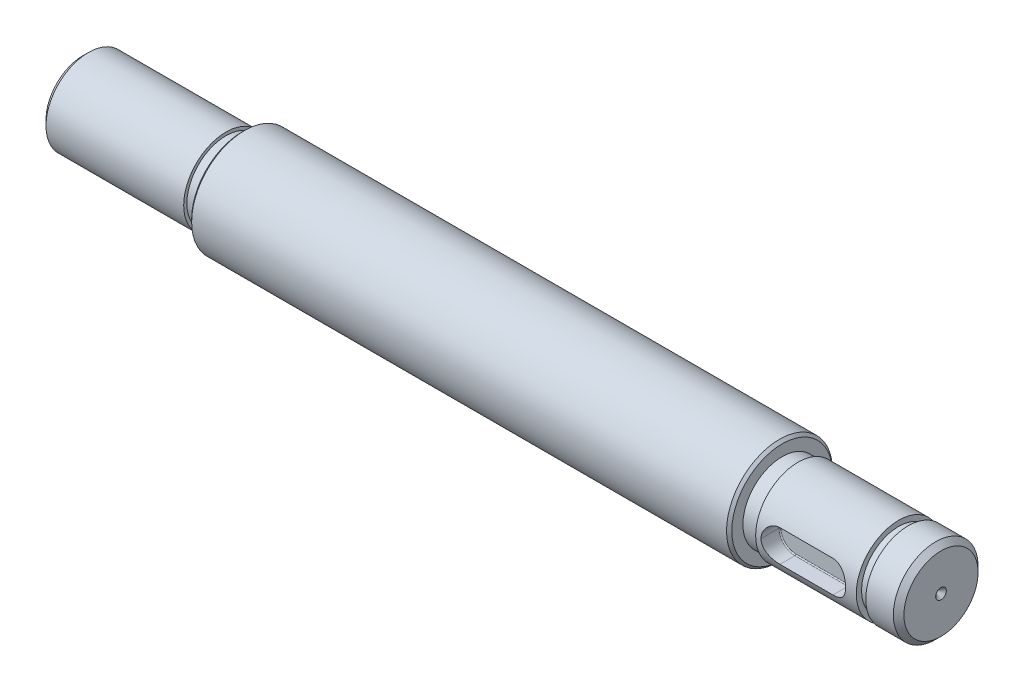
SolidWorks part; units mm, degrees
ref_plane "Front Plane" through (0, 0, 0) normal (0, 0, 1) x (1, 0, 0)
ref_plane "Top Plane" through (0, 0, 0) normal (0, 1, 0) x (1, 0, 0)
ref_plane "Right Plane" through (0, 0, 0) normal (1, 0, 0) x (0, 0, -1)
sketch "Sketch1" plane through (0, 0, 0) normal (0, 0, 1) x (1, 0, 0)
  line L0 (0, 0) -> (81, 0) construction
  line L1 (0, 4) -> (15, 4)
  line L2 (15, 4) -> (15, 4.75)
  line L3 (15.25, 5) -> (65.75, 5)
  line L4 (66, 4.75) -> (66, 4)
  line L5 (66, 4) -> (81, 4)
  line L6 (0, 4) -> (0, 0)
  line L7 (81, 0) -> (81, 4)
  line L8 (65.75, 5) -> (66, 4.75)
  line L9 (15, 4.75) -> (15.25, 5)
  line L10 (81, 0) -> (0, 0)
  dimension "D1" = 45
  dimension "D" = 10
  dimension "L_s_1" = 51
  dimension "LA" = 15
  dimension "LB" = 15
  dimension "L" = 81
  dimension "D2" = 45
revolve "Revolve1" add sketch "Sketch1" angle 360 about L0
cosmetic thread "Cosmetic Thread1" [suppressed] parameters "MA"=5, "TD_s"=6.619
cosmetic thread "Cosmetic Thread2" [suppressed] parameters "MSA"=5, "TD_s"=6.619
cosmetic thread "Cosmetic Thread3" [suppressed] parameters "MMA"=5, "TD_s"=6.619
cosmetic thread "Cosmetic Thread4" [suppressed] parameters "MC"=5, "TD_s"=8.344
cosmetic thread "Cosmetic Thread5" [suppressed] parameters "MSC"=5, "TD_s"=8.344
cosmetic thread "Cosmetic Thread6" [suppressed] parameters "MMC"=5, "TD_s"=8.344
cosmetic thread "Cosmetic Thread7" [suppressed] parameters "MD"=5, "TD_s"=8.344
cosmetic thread "Cosmetic Thread8" [suppressed] parameters "MSD"=5, "TD_s"=8.344
cosmetic thread "Cosmetic Thread9" [suppressed] parameters "MMD"=5, "TD_s"=8.344
cosmetic thread "Cosmetic Thread10" [suppressed] parameters "MB"=5, "TD_s"=6.619
cosmetic thread "Cosmetic Thread11" [suppressed] parameters "MSB"=5, "TD_s"=6.619
cosmetic thread "Cosmetic Thread12" [suppressed] parameters "MMB"=5, "TD_s"=6.619
chamfer "Chamfer1" distance 0.5 angle 45 2 edges at (81, 0, 4) (0, 0, 4)
sketch "Sketch2" plane through (0, 0, 0) normal (0, 0, 1) x (1, 0, 0)
  line L0 (0, 0) -> (81, 0) construction
  line L1 (81, -4) -> (81, 4) construction
  line L2 (0, 0.5) -> (0.5, 0)
  line L3 (0, 4) -> (0, -4) construction
  line L4 (0.5, 0) -> (0, 0)
  line L5 (0, 0) -> (0, 0.5)
  line L6 (81, 0) -> (81, 0.5)
  line L7 (81, 0.5) -> (80.5, 0)
  line L8 (80.5, 0) -> (81, 0)
  dimension "D1" = 1
  dimension "D2" = 0.5
revolve "Cut-Revolve1" cut sketch "Sketch2" angle 360 about L0
sketch "Sketch3" plane through (0, 0, 0) normal (0, 0, 1) x (1, 0, 0)
  line L0 (0, 0) -> (81, 0) construction
  line L1 (81, -4) -> (81, 4) construction
  line L2 (15, 4) -> (15, 4.75) construction
  line L3 (13.5, 4) -> (15, 4)
  line L4 (13.5, 4) -> (13.5, 3.7)
  line L5 (13.5, 3.7) -> (15, 3.7)
  line L6 (15, 4) -> (15, 3.7)
  line L7 (66, 4) -> (67.5, 4)
  line L8 (66, 4) -> (66, 3.7)
  line L9 (66, 3.7) -> (67.5, 3.7)
  line L10 (67.5, 4) -> (67.5, 3.7)
  line L11 (0, 4) -> (15, 4) construction
  line L12 (66, 4.75) -> (66, 4) construction
  line L13 (66, 4) -> (81, 4) construction
  dimension "D1" = 1.5
  dimension "D2" = 0.3
  dimension "D3" = 1.5
revolve "Cut-Revolve2" cut sketch "Sketch3" angle 360 about L0
ref_plane "Plane1" through (0, 0, 5) normal (0, 0, 1) x (1, 0, 0)
ref_plane "Plane2" through (0, 0, 4) normal (0, 0, 1) x (1, 0, 0)
ref_plane "Plane3" through (15, 0, 0) normal (1, 0, 0) x (0, 0, -1)
ref_plane "Plane4" through (81, 0, 0) normal (1, 0, 0) x (0, 0, -1)
other "DeleteFace1" [suppressed]
other "DeleteFace2" [suppressed]
other "DeleteFace3" [suppressed]
sketch "Sketch4" [suppressed] plane through (0, 0, 0) normal (0, 0, 1) x (1, 0, 0)
  line L1 (12, 0) -> (38, 0)
  line L2 (12, 0) -> (12, 5)
  line L3 (12, 5) -> (38, 5)
  line L4 (38, 0) -> (38, 5)
  line L5 (38, 4.75) -> (38, 4) construction
  line L6 (12.25, 5) -> (37.75, 5) construction
  line L7 (0, 0) -> (50, 0) construction
  line L8 (12, 4) -> (12, 4.75) construction
revolve "Revolve2" [suppressed] add sketch "Sketch4" angle 360 about L7
sketch "Sketch5" [suppressed] plane through (0, 0, 0) normal (0, 0, 1) x (1, 0, 0)
  line L0 (0, 0) -> (50, 0) construction
  line L2 (50, 0) -> (50, 4) construction
  line L3 (12, 0) -> (38, 0)
  line L4 (12, 0) -> (12, 5)
  line L5 (12, 5) -> (38, 5)
  line L6 (38, 0) -> (38, 5)
  line L7 (12.25, 5) -> (37.75, 5) construction
  line L8 (38, 4.75) -> (38, 4) construction
  line L9 (12, 4) -> (12, 4.75) construction
revolve "Revolve3" [suppressed] add sketch "Sketch5" angle 360 about L0
sketch "Sketch6" [suppressed] plane through (0, 0, 0) normal (0, 0, 1) x (1, 0, 0)
  line L0 (0, 0) -> (50, 0) construction
  line L2 (12, 0) -> (38, 0)
  line L3 (12, 0) -> (12, 5)
  line L4 (12, 5) -> (38, 5)
  line L5 (38, 0) -> (38, 5)
  line L6 (38, 4.75) -> (38, 4) construction
  line L7 (12.25, 5) -> (37.75, 5) construction
  line L8 (12, 4) -> (12, 4.75) construction
revolve "Revolve4" [suppressed] add sketch "Sketch6" angle 360 about L0
sketch "Sketch7" [suppressed] plane through (0, 0, 0) normal (0, 0, 1) x (1, 0, 0)
  line L0 (0, 0) -> (50, 0) construction
  line L2 (12, 0) -> (38, 0)
  line L3 (12, 0) -> (12, 5)
  line L4 (12, 5) -> (38, 5)
  line L5 (38, 0) -> (38, 5)
  line L6 (38, 4.75) -> (38, 4) construction
  line L7 (12.25, 5) -> (37.75, 5) construction
  line L8 (12, 4) -> (12, 4.75) construction
revolve "Revolve5" [suppressed] add sketch "Sketch7" angle 360 about L0
sketch "Sketch8" [suppressed] plane through (0, 0, 0) normal (0, 0, 1) x (1, 0, 0)
  line L0 (0, 0) -> (50, 0) construction
  line L2 (12, 0) -> (38, 0)
  line L3 (12, 0) -> (12, 5)
  line L4 (12, 5) -> (38, 5)
  line L5 (38, 0) -> (38, 5)
  line L6 (38, 4.75) -> (38, 4) construction
  line L7 (12.25, 5) -> (37.75, 5) construction
  line L8 (12, 4) -> (12, 4.75) construction
revolve "Revolve6" [suppressed] add sketch "Sketch8" angle 360 about L0
sketch "Sketch9" [suppressed] plane through (0, 0, 0) normal (0, 0, 1) x (1, 0, 0)
  line L0 (0, 0) -> (50, 0) construction
  line L2 (12, 0) -> (38, 0)
  line L3 (12, 0) -> (12, 5)
  line L4 (12, 5) -> (38, 5)
  line L5 (38, 0) -> (38, 5)
  line L6 (38, 4.75) -> (38, 4) construction
  line L7 (12.25, 5) -> (37.75, 5) construction
  line L8 (12, 4) -> (12, 4.75) construction
revolve "Revolve7" [suppressed] add sketch "Sketch9" angle 360 about L0
other "DeleteFace4" [suppressed]
other "DeleteFace5" [suppressed]
other "DeleteFace6" [suppressed]
hole_wizard "Tapped Hole1" [suppressed] positions "Sketch11" profile "Sketch10" tap size "M3x0.5" standard "JIS"
sketch "Sketch11" [suppressed] plane through (0, 0, 0) normal (-1, 0, 0) x (0, 0, 1)
  point P0 (0, 0)
sketch "Sketch10" [suppressed] plane through (0, 0, 0) normal (0, 1, 0) x (0, 0, 1)
  line L0 (0, 0) -> (0, 9.2511)
  line L1 (0, 9.2511) -> (1.25, 8.5)
  line L2 (1.25, 8.5) -> (1.25, 0)
  line L5 (1.25, 0) -> (0, 0)
  line L10 (0, 9.2511) -> (-1.25, 8.5) construction
  line L11 (0, 0) -> (0, 9.2511) construction
  dimension "Tap Drill Dia." = 2.5
  dimension "Tap Drill Depth" = 8.5
  dimension "Drill Angle" = 118
cosmetic thread "Hole Thread1" [suppressed] parameters "NAx2"=6, "NA"=3
hole_wizard "Tapped Hole2" [suppressed] positions "Sketch13" profile "Sketch12" tap size "M3x0.5" standard "JIS"
sketch "Sketch13" [suppressed] plane through (50, 0, 0) normal (1, 0, 0) x (0, 0, -1)
  point P0 (0, 0)
sketch "Sketch12" [suppressed] plane through (50, 0, 0) normal (0, 1, 0) x (0, 0, -1)
  line L0 (0, 0) -> (0, 9.2511)
  line L1 (0, 9.2511) -> (1.25, 8.5)
  line L2 (1.25, 8.5) -> (1.25, 0)
  line L5 (1.25, 0) -> (0, 0)
  line L10 (0, 9.2511) -> (-1.25, 8.5) construction
  line L11 (0, 0) -> (0, 9.2511) construction
  dimension "Tap Drill Dia." = 2.5
  dimension "Tap Drill Depth" = 8.5
  dimension "Drill Angle" = 118
cosmetic thread "Hole Thread2" [suppressed] parameters "NBx2"=6, "NB"=3
ref_plane "Dim. KA" [suppressed] through (2, 0, 0) normal (1, 0, 0) x (0, 0, -1)
sketch "Sketch14" [suppressed] plane through (0, 0, 4) normal (0, 0, 1) x (1, 0, 0)
  line L0 (6, 0) -> (2, 0) construction
  line L1 (2, 1) -> (6, 1)
  line L2 (2, 1) -> (2, -1)
  line L3 (2, -1) -> (6, -1)
  line L4 (6, 1) -> (6, -1)
  line L6 (2, -5.5) -> (2, 5.5) construction
  dimension "B_s_1" = 3
  dimension "HA_1" = 4
extrude "Cut-Extrude1" [suppressed] cut sketch "Sketch14" against normal blind 1.8
fillet "Fillet1" [suppressed] radius 1.5
fillet "Fillet2" [suppressed] radius 1.5
fillet "Fillet3" [suppressed] radius 0.1
ref_plane "Dim. KC" [suppressed] through (14, 0, 0) normal (1, 0, 0) x (0, 0, -1)
sketch "Sketch15" [suppressed] plane through (0, 0, 5) normal (0, 0, 1) x (1, 0, 0)
  line L0 (18, 0) -> (14, 0) construction
  line L1 (14, 1.5) -> (18, 1.5)
  line L2 (14, 1.5) -> (14, -1.5)
  line L3 (14, -1.5) -> (18, -1.5)
  line L4 (18, 1.5) -> (18, -1.5)
  line L6 (14, -5.5) -> (14, 5.5) construction
  dimension "B_s_2" = 3
  dimension "HC_1" = 4
extrude "Cut-Extrude2" [suppressed] cut sketch "Sketch15" against normal blind 1.8
fillet "Fillet4" [suppressed] radius 1.5
fillet "Fillet5" [suppressed] radius 1.5
fillet "Fillet6" [suppressed] radius 0.1
sketch "Sketch16" [suppressed] plane through (0, 0, 5) normal (0, 0, 1) x (1, 0, 0)
  line L0 (31, 0) -> (27, 0) construction
  line L1 (27, 1.5) -> (31, 1.5)
  line L2 (27, 1.5) -> (27, -1.5)
  line L3 (27, -1.5) -> (31, -1.5)
  line L4 (31, 1.5) -> (31, -1.5)
  line L5 (12, 4) -> (12, 4.75) construction
  dimension "HD_1" = 4
  dimension "B_s_2" = 3
  dimension "KD" = 15
extrude "Cut-Extrude3" [suppressed] cut sketch "Sketch16" against normal blind 1.8
fillet "Fillet7" [suppressed] radius 1.5
fillet "Fillet8" [suppressed] radius 1.5
fillet "Fillet9" [suppressed] radius 0.1
ref_plane "Dim. KB" through (76, 0, 0) normal (1, 0, 0) x (0, 0, -1)
sketch "Sketch17" plane through (0, 0, 4) normal (0, 0, 1) x (1, 0, 0)
  line L0 (76, -5.5) -> (76, 5.5) construction
  line L1 (68, 1.5) -> (76, 1.5)
  line L2 (68, 1.5) -> (68, -1.5)
  line L3 (68, -1.5) -> (76, -1.5)
  line L4 (76, 1.5) -> (76, -1.5)
  line L7 (68, 0) -> (76, 0) construction
  dimension "HB_1" = 8
  dimension "B_s_1" = 3
extrude "Cut-Extrude4" cut sketch "Sketch17" against normal blind 1.8
fillet "Fillet10" radius 1.5 2 edges at (76, 1.5, 2.954) (76, -1.5, 2.954)
fillet "Fillet11" radius 1.5 2 edges at (68, 1.5, 2.954) (68, -1.5, 2.954)
fillet "Fillet12" radius 0.1 6 edges at (72, -1.5, 2.2) (72, 1.5, 2.2) (75.5607, 1.0607, 2.2) (75.5607, -1.0607, 2.2) (68.4393, -1.0607, 2.2) (68.4393, 1.0607, 2.2)
ref_plane "Dim. ZA" [suppressed] through (2, 0, 0) normal (1, 0, 0) x (0, 0, -1)
ref_plane "Dim. AA_1" [suppressed] through (0, 0, 0) normal (0, -1, 0) x (1, 0, 0)
sketch "Sketch18" [suppressed] plane through (0, 0, 4) normal (0, 0, 1) x (1, 0, 0)
  line L0 (6, 0) -> (2, 0) construction
  line L1 (2, 1) -> (6, 1)
  line L2 (2, 1) -> (2, -1)
  line L3 (2, -1) -> (6, -1)
  line L4 (6, 1) -> (6, -1)
  line L6 (2, -5.5) -> (2, 5.5) construction
  dimension "B_s_1" = 3
  dimension "HA_2" = 4
extrude "Cut-Extrude5" [suppressed] cut sketch "Sketch18" against normal blind 1.8
fillet "Fillet13" [suppressed] radius 1.5
fillet "Fillet14" [suppressed] radius 1.5
fillet "Fillet15" [suppressed] radius 0.1
sketch "Sketch19" [suppressed] plane through (0, 0, 0) normal (0, -1, 0) x (1, 0, 0)
  line L0 (2, 4) -> (6, 4) construction
  line L1 (2, -3) -> (6, -3)
  line L2 (2, -3) -> (2, -4)
  line L3 (2, -4) -> (6, -4)
  line L4 (6, -3) -> (6, -4)
  line L5 (2, -5.5) -> (2, 5.5) construction
  line L6 (0, 0) -> (6, 0) construction
  dimension "H_1" = 1
  dimension "P" = 8
extrude "Cut-Extrude6" [suppressed] cut sketch "Sketch19" against normal through all and the other way through all
ref_plane "Dim. ZC" [suppressed] through (14, 0, 0) normal (1, 0, 0) x (0, 0, -1)
ref_plane "Dim. AC_1" [suppressed] through (0, 0, 0) normal (0, -1, 0) x (1, 0, 0)
sketch "Sketch20" [suppressed] plane through (0, 0, 5) normal (0, 0, 1) x (1, 0, 0)
  line L0 (14, 0) -> (18, 0) construction
  line L1 (14, 1.5) -> (18, 1.5)
  line L2 (14, 1.5) -> (14, -1.5)
  line L3 (14, -1.5) -> (18, -1.5)
  line L4 (18, 1.5) -> (18, -1.5)
  line L6 (14, -5.5) -> (14, 5.5) construction
  dimension "HC_2" = 4
  dimension "B_s_2" = 3
extrude "Cut-Extrude7" [suppressed] cut sketch "Sketch20" against normal blind 1.8
fillet "Fillet16" [suppressed] radius 1.5
fillet "Fillet17" [suppressed] radius 1.5
fillet "Fillet18" [suppressed] radius 0.1
sketch "Sketch21" [suppressed] plane through (0, 0, 0) normal (0, -1, 0) x (1, 0, 0)
  line L0 (14, -5.5) -> (14, 5.5) construction
  line L1 (14, -4) -> (18, -4)
  line L2 (14, -4) -> (14, -5)
  line L3 (14, -5) -> (18, -5)
  line L4 (18, -4) -> (18, -5)
  line L5 (14, 5) -> (18, 5) construction
  line L6 (0, 0) -> (18, 0) construction
  dimension "H_2" = 1
  dimension "D" = 10
extrude "Cut-Extrude8" [suppressed] cut sketch "Sketch21" against normal through all and the other way through all
ref_plane "Dim. AD" [suppressed] through (0, 0, 0) normal (0, -1, 0) x (1, 0, 0)
sketch "Sketch22" [suppressed] plane through (0, 0, 5) normal (0, 0, 1) x (1, 0, 0)
  line L0 (27, 0) -> (31, 0) construction
  line L1 (27, 1.5) -> (31, 1.5)
  line L2 (27, 1.5) -> (27, -1.5)
  line L3 (27, -1.5) -> (31, -1.5)
  line L4 (31, 1.5) -> (31, -1.5)
  line L6 (12, 4) -> (12, 4.75) construction
  dimension "B_s_2" = 3
  dimension "HD_2" = 4
  dimension "ZD" = 15
extrude "Cut-Extrude9" [suppressed] cut sketch "Sketch22" against normal blind 1.8
fillet "Fillet19" [suppressed] radius 1.5
fillet "Fillet20" [suppressed] radius 1.5
fillet "Fillet21" [suppressed] radius 0.08
sketch "Sketch23" [suppressed] plane through (0, 0, 0) normal (0, -1, 0) x (1, 0, 0)
  line L1 (27, -4) -> (31, -4)
  line L2 (27, -4) -> (27, -5)
  line L3 (27, -5) -> (31, -5)
  line L4 (31, -4) -> (31, -5)
  line L5 (27, 5) -> (31, 5) construction
  line L6 (0, 0) -> (31, 0) construction
  dimension "H_2" = 1
  dimension "D" = 10
extrude "Cut-Extrude10" [suppressed] cut sketch "Sketch23" against normal through all and the other way through all
ref_plane "Dim. ZB" [suppressed] through (48, 0, 0) normal (1, 0, 0) x (0, 0, -1)
ref_plane "Dim. AB_1" [suppressed] through (0, 0, 0) normal (0, -1, 0) x (1, 0, 0)
sketch "Sketch24" [suppressed] plane through (0, 0, 4) normal (0, 0, 1) x (1, 0, 0)
  line L0 (45, 0) -> (48, 0) construction
  line L1 (45, 1) -> (48, 1)
  line L2 (45, 1) -> (45, -1)
  line L3 (45, -1) -> (48, -1)
  line L4 (48, 1) -> (48, -1)
  line L5 (48, -5.5) -> (48, 5.5) construction
  dimension "B_s_1" = 3
  dimension "HB_2" = 3
extrude "Cut-Extrude11" [suppressed] cut sketch "Sketch24" against normal blind 1.8
fillet "Fillet22" [suppressed] radius 1.5
fillet "Fillet23" [suppressed] radius 1.5
fillet "Fillet24" [suppressed] radius 0.1
sketch "Sketch25" [suppressed] plane through (0, 0, 0) normal (0, -1, 0) x (1, 0, 0)
  line L0 (45, 4) -> (48, 4) construction
  line L1 (45, -3) -> (48, -3)
  line L2 (45, -3) -> (45, -4)
  line L3 (45, -4) -> (48, -4)
  line L4 (48, -3) -> (48, -4)
  line L5 (48, -5.5) -> (48, 5.5) construction
  line L6 (0, 0) -> (48, 0) construction
  line L8 (50, 0) -> (0, 0) construction
  dimension "H_1" = 1
  dimension "P" = 8
extrude "Cut-Extrude12" [suppressed] cut sketch "Sketch25" against normal through all and the other way through all
sketch "Sketch26" [suppressed] plane through (0, 0, 0) normal (0, 0, 1) x (1, 0, 0)
  line L1 (3.1, 4) -> (4, 4)
  line L2 (3.1, 4) -> (3.1, 3.5)
  line L3 (3.1, 3.5) -> (4, 3.5)
  line L4 (4, 4) -> (4, 3.5)
  line L5 (0, 0) -> (50, 0) construction
  line L7 (0, 4) -> (0, 0) construction
  line L9 (50, 0) -> (0, 0) construction
  line L10 (0, 4) -> (12, 4) construction
  dimension "D_s_1" = 7
  dimension "TA" = 4
  dimension "M_s_1" = 0.9
revolve "Cut-Revolve3" [suppressed] cut sketch "Sketch26" angle 360 about L5
sketch "Sketch27" [suppressed] plane through (0, 0, 0) normal (0, 0, 1) x (1, 0, 0)
  line L0 (0, 0) -> (50, 0) construction
  line L1 (14.85, 5) -> (16, 5)
  line L2 (14.85, 5) -> (14.85, 4.8)
  line L3 (14.85, 4.8) -> (16, 4.8)
  line L4 (16, 5) -> (16, 4.8)
  line L5 (12.25, 5) -> (37.75, 5) construction
  line L7 (12, 4) -> (12, 4.75) construction
  dimension "D_s_2" = 9.6
  dimension "TC" = 4
  dimension "M_s_2" = 1.15
revolve "Cut-Revolve4" [suppressed] cut sketch "Sketch27" angle 360 about L0
sketch "Sketch28" [suppressed] plane through (0, 0, 0) normal (0, 0, 1) x (1, 0, 0)
  line L0 (0, 0) -> (50, 0) construction
  line L2 (38, 4.75) -> (38, 4) construction
  line L3 (34, 5) -> (35.15, 5)
  line L4 (34, 5) -> (34, 4.8)
  line L5 (34, 4.8) -> (35.15, 4.8)
  line L6 (35.15, 5) -> (35.15, 4.8)
  line L7 (12.25, 5) -> (37.75, 5) construction
  dimension "TD" = 4
  dimension "M_s_2" = 1.15
  dimension "D_s_2" = 9.6
revolve "Cut-Revolve5" [suppressed] cut sketch "Sketch28" angle 360 about L0
sketch "Sketch29" plane through (0, 0, 0) normal (0, 0, 1) x (1, 0, 0)
  line L0 (81, 0) -> (0, 0) construction
  line L3 (81, 0) -> (81, 4) construction
  line L4 (77, 4) -> (77.9, 4)
  line L5 (77, 4) -> (77, 3.5)
  line L6 (77, 3.5) -> (77.9, 3.5)
  line L7 (77.9, 4) -> (77.9, 3.5)
  line L8 (66, 4) -> (81, 4) construction
  line L9 (81, 0) -> (0, 0) construction
  dimension "TB" = 4
  dimension "M_s_1" = 0.9
  dimension "D_s_1" = 7
revolve "Cut-Revolve6" cut sketch "Sketch29" angle 360 about L0
ref_plane "Dim. SA" [suppressed] through (2, 0, 0) normal (1, 0, 0) x (0, 0, -1)
sketch "Sketch30" [suppressed] plane through (0, 0, 0) normal (0, 1, 0) x (1, 0, 0)
  line L0 (0, 0) -> (10, 0) construction
  line L1 (2, 4) -> (10, 4)
  line L2 (2, 4) -> (2, 3.5)
  line L3 (2, 3.5) -> (10, 3.5)
  line L4 (10, 4) -> (10, 3.5)
  line L5 (2, -3.5) -> (10, -3.5)
  line L6 (2, -3.5) -> (2, -4)
  line L7 (2, -4) -> (10, -4)
  line L8 (10, -3.5) -> (10, -4)
  line L9 (0, 0) -> (50, 0) construction
  line L10 (10.5, 4) -> (0, 4) construction
  line L11 (-9.162, -4) -> (9.162, -4) construction
  line L12 (50, 0) -> (0, 0) construction
  line L16 (2, -5.5) -> (2, 5.5) construction
  dimension "W1" = 7
  dimension "L_s_2" = 8
extrude "Cut-Extrude13" [suppressed] cut sketch "Sketch30" against normal through all and the other way through all
ref_plane "Dim. SD" [suppressed] through (14, 0, 0) normal (1, 0, 0) x (0, 0, -1)
sketch "Sketch31" [suppressed] plane through (0, 0, 0) normal (0, 1, 0) x (1, 0, 0)
  line L0 (50, 0) -> (0, 0) construction
  line L1 (14, 4) -> (22, 4)
  line L2 (14, 4) -> (14, 5)
  line L3 (14, 5) -> (22, 5)
  line L4 (22, 4) -> (22, 5)
  line L5 (14, -4) -> (22, -4)
  line L6 (14, -4) -> (14, -5)
  line L7 (14, -5) -> (22, -5)
  line L8 (22, -4) -> (22, -5)
  line L10 (50, 0) -> (0, 0) construction
  line L11 (-7.8264, -5) -> (7.8264, -5) construction
  line L20 (14, -5.5) -> (14, 5.5) construction
  dimension "W" = 8
  dimension "L_s_3" = 8
  dimension "D" = 10
extrude "Cut-Extrude14" [suppressed] cut sketch "Sketch31" against normal through all and the other way through all
ref_plane "Dim. SB" [suppressed] through (48, 0, 0) normal (1, 0, 0) x (0, 0, -1)
sketch "Sketch32" [suppressed] plane through (0, 0, 0) normal (0, 1, 0) x (1, 0, 0)
  line L0 (40, 0) -> (48, 0) construction
  line L1 (40, 4) -> (48, 4)
  line L2 (40, 4) -> (40, 3.5)
  line L3 (40, 3.5) -> (48, 3.5)
  line L4 (48, 4) -> (48, 3.5)
  line L5 (40, -3.5) -> (48, -3.5)
  line L6 (40, -3.5) -> (40, -4)
  line L7 (40, -4) -> (48, -4)
  line L8 (48, -3.5) -> (48, -4)
  line L10 (48, -5.5) -> (48, 5.5) construction
  line L12 (-9.162, -4) -> (9.162, -4) construction
  line L13 (50, 0) -> (0, 0) construction
  dimension "L_s_2" = 8
  dimension "W1" = 7
  dimension "D" = 10
extrude "Cut-Extrude15" [suppressed] cut sketch "Sketch32" against normal through all and the other way through all
ref_plane "Dim. WA" [suppressed] through (2, 0, 0) normal (1, 0, 0) x (0, 0, -1)
ref_plane "Dim. GA" [suppressed] through (6, 0, 0) normal (1, 0, 0) x (0, 0, -1)
sketch "Sketch33" [suppressed] plane through (2, 0, 0) normal (1, 0, 0) x (0, 0, -1)
  line L0 (-3, 2.6458) -> (-3, -2.6458)
  line L1 (-4, 0) -> (4, 0) construction
  circle A0 centre (0, 0) radius 4 construction
  arc A1 (-3, 2.6458) -> (-3, -2.6458) centre (0, 0) ccw
  dimension "H_1" = 1
extrude "Cut-Extrude16" [suppressed] cut sketch "Sketch33" along normal up to surface (4 mm away)
sketch "Sketch34" [suppressed] plane through (2, 0, 0) normal (1, 0, 0) x (0, 0, -1)
  line L0 (4, 0) -> (-4, 0) construction
  line L1 (0, -4) -> (0, 4) construction
  line L2 (0, 0) -> (-2, -3.4641) construction
  line L3 (-3.7913, -1.2752) -> (0.7913, -3.921)
  arc A0 (-3.7913, -1.2752) -> (0.7913, -3.921) centre (0, 0) ccw
  dimension "AA_2" = 60
  dimension "H_1" = 1
extrude "Cut-Extrude17" [suppressed] cut sketch "Sketch34" along normal up to surface (4 mm away)
ref_plane "Dim. WC" [suppressed] through (14, 0, 0) normal (1, 0, 0) x (0, 0, -1)
ref_plane "Dim. GC" [suppressed] through (18, 0, 0) normal (1, 0, 0) x (0, 0, -1)
sketch "Sketch35" [suppressed] plane through (14, 0, 0) normal (1, 0, 0) x (0, 0, -1)
  line L0 (-4, 3) -> (-4, -3)
  line L1 (-5, 0) -> (5, 0) construction
  circle A0 centre (0, 0) radius 5 construction
  arc A1 (-4, 3) -> (-4, -3) centre (0, 0) ccw
  dimension "H_2" = 1
extrude "Cut-Extrude18" [suppressed] cut sketch "Sketch35" along normal up to surface (4 mm away)
sketch "Sketch36" [suppressed] plane through (14, 0, 0) normal (1, 0, 0) x (0, 0, -1)
  line L0 (5, 0) -> (-5, 0) construction
  line L1 (0, -5) -> (0, 5) construction
  line L2 (0, 0) -> (-2.5, -4.3301) construction
  line L3 (-4.5981, -1.9641) -> (0.5981, -4.9641)
  arc A0 (-4.5981, -1.9641) -> (0.5981, -4.9641) centre (0, 0) ccw
  dimension "AC_2" = 60
  dimension "H_2" = 1
extrude "Cut-Extrude19" [suppressed] cut sketch "Sketch36" along normal up to surface (4 mm away)
ref_plane "Dim. WB" [suppressed] through (48, 0, 0) normal (1, 0, 0) x (0, 0, -1)
ref_plane "Dim. GB" [suppressed] through (44, 0, 0) normal (1, 0, 0) x (0, 0, -1)
sketch "Sketch37" [suppressed] plane through (48, 0, 0) normal (1, 0, 0) x (0, 0, -1)
  line L0 (-3, 2.6458) -> (-3, -2.6458)
  line L1 (-4, 0) -> (4, 0) construction
  circle A0 centre (0, 0) radius 4 construction
  arc A1 (-3, 2.6458) -> (-3, -2.6458) centre (0, 0) ccw
  dimension "H_1" = 1
extrude "Cut-Extrude20" [suppressed] cut sketch "Sketch37" against normal up to surface (4 mm away)
sketch "Sketch38" [suppressed] plane through (48, 0, 0) normal (1, 0, 0) x (0, 0, -1)
  line L0 (4, 0) -> (-4, 0) construction
  line L1 (0, -4) -> (0, 4) construction
  line L2 (0, 0) -> (-2, -3.4641) construction
  line L3 (-3.7913, -1.2752) -> (0.7913, -3.921)
  arc A0 (-3.7913, -1.2752) -> (0.7913, -3.921) centre (0, 0) ccw
  dimension "AB_2" = 60
  dimension "H_1" = 1
extrude "Cut-Extrude21" [suppressed] cut sketch "Sketch38" against normal up to surface (4 mm away)
equation "\"D1@Fillet1\" = \"B_s_1@Sketch14\" / 2"
equation "\"D1@Fillet4\"= \"B_s_2@Sketch15\" / 2"
equation "\"D1@Fillet7\"= \"B_s_2@Sketch16\" / 2"
equation "\"D1@Fillet10\" = \"B_s_1@Sketch17\" / 2"
equation "\"D1@Fillet13\" = \"B_s_1@Sketch18\" / 2"
equation "\"D1@Fillet16\" = \"B_s_2@Sketch20\" / 2"
equation "\"D1@Fillet19\" = \"B_s_2@Sketch22\" / 2"
equation "\"D1@Fillet22\" = \"B_s_1@Sketch24\" / 2"
equation "\"D1@Fillet2\" = \"B_s_1@Sketch14\" / 2"
equation "\"D1@Fillet5\" = \"B_s_2@Sketch15\" / 2"
equation "\"D1@Fillet8\" = \"B_s_2@Sketch16\" / 2"
equation "\"D1@Fillet11\" = \"B_s_1@Sketch17\" / 2"
equation "\"Plane dim_1\"= \"D@Sketch1\" * 0.5"
equation "\"Plane dim_2\"= \"P@Sketch1\" * 0.5"
equation "\"D1@Fillet14\" = \"B_s_1@Sketch18\" / 2"
equation "\"D1@Fillet17\" = \"B_s_2@Sketch20\" / 2"
equation "\"D1@Fillet20\" = \"B_s_2@Sketch22\" / 2"
equation "\"D1@Fillet23\" = \"B_s_1@Sketch24\" / 2"
